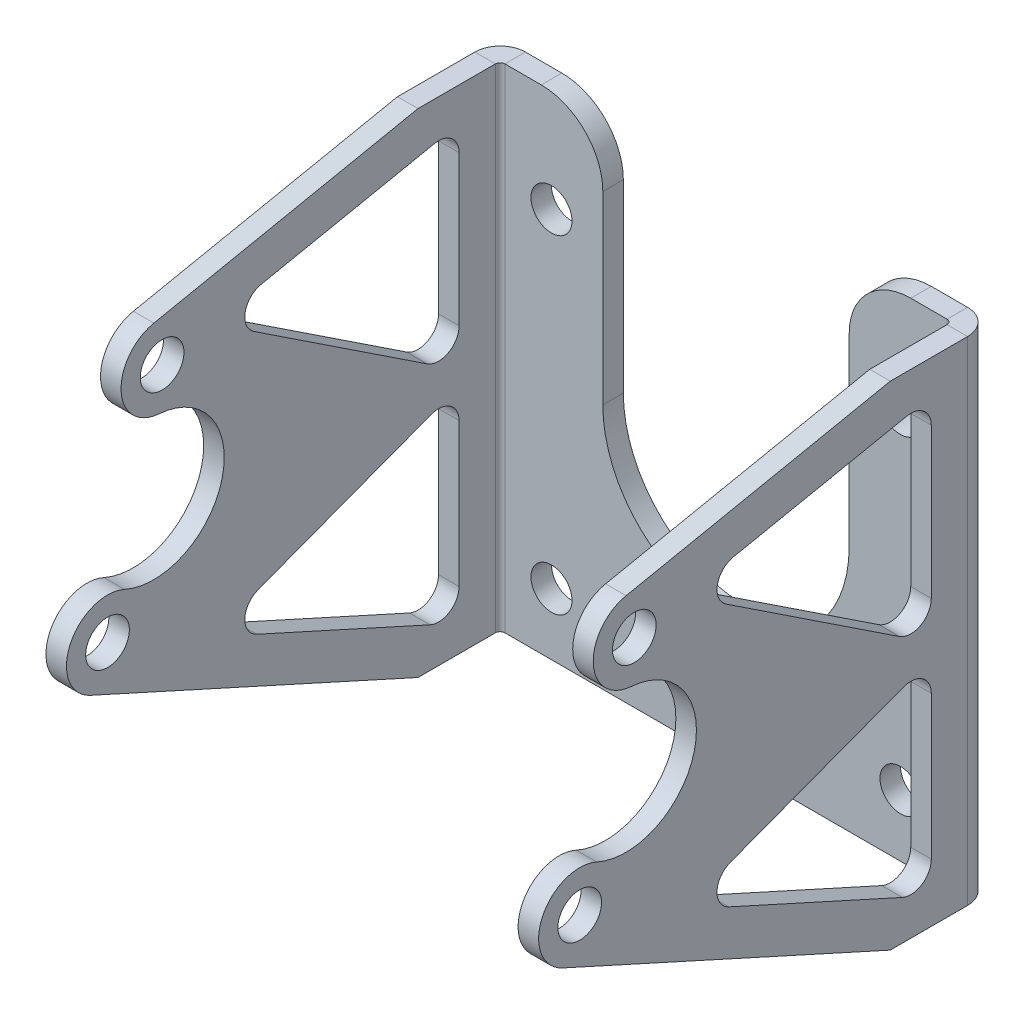
SolidWorks part; units mm, degrees
note: The reader was unsure of these and kept them because the rebuilt part matched: flange length of "Edge-Flange1".
ref_plane "Front Plane" through (0, 0, 0) normal (0, 0, 1) x (1, 0, 0)
ref_plane "Top Plane" through (0, 0, 0) normal (0, 1, 0) x (1, 0, 0)
ref_plane "Right Plane" through (0, 0, 0) normal (1, 0, 0) x (0, 0, -1)
sketch "Sketch4" plane through (0, 0, 0) normal (0, 0, 1) x (1, 0, 0)
  line L7 (38.4703, 37.2498) -> (28.9453, 37.2498)
  line L8 (19.4203, 27.7248) -> (19.4203, -0.8502)
  line L9 (-18.6797, -0.8502) -> (-18.6797, 27.7248)
  line L10 (-28.2047, 37.2498) -> (-37.7297, 37.2498)
  line L11 (-37.7297, 37.2498) -> (-37.7297, -38.9502)
  line L12 (-37.7297, -38.9502) -> (38.4703, -38.9502)
  line L13 (38.4703, -38.9502) -> (38.4703, 37.2498)
  arc A7 (28.9453, 37.2498) -> (19.4203, 27.7248) centre (28.9453, 27.7248) ccw
  arc A8 (-18.6797, -0.8502) -> (19.4203, -0.8502) centre (0.3703, -0.8502) ccw
  arc A9 (-18.6797, 27.7248) -> (-28.2047, 37.2498) centre (-28.2047, 27.7248) ccw
  circle A10 centre (-26.6172, -29.4252) radius 3.175
  circle A11 centre (27.3578, -29.4252) radius 3.175
  circle A12 centre (27.3578, 21.3748) radius 3.175
  circle A13 centre (-26.6172, 21.3748) radius 3.175
base flange "Base-Flange1" sketch "Sketch4" thickness 3.175 reverse thickness direction no parameters "D1"=0.7366
edge flange "Edge-Flange1" sketch "Sketch11" flange profiles "Sketch11", "Sketch20" flange angle 90 flange length 76.2 flange position material inside bend radius 0.7366 thickness 3.175 relief rectangular parameters "D6"=10, "D8"=0.254
sketch "Sketch11" plane through (38.4703, 0, 0) normal (-1, 0, 0) x (0, -1, 0)
  line L2 (-37.2498, 0) -> (-37.2498, 73.025)
  line L3 (-37.2498, 73.025) -> (38.9502, 73.025)
  line L4 (38.9502, 73.025) -> (38.9502, 0)
  line L5 (38.9502, 0) -> (-37.2498, 0) construction
  line L6 (38.9502, 0) -> (-37.2498, 0)
sketch "Sketch20" plane through (-37.7297, 0, 0) normal (1, 0, 0) x (0, 1, 0)
  line L0 (37.2498, 0) -> (-38.9502, 0) construction
  line L1 (37.2498, 0) -> (-38.9502, 0)
  line L2 (37.2498, 0) -> (37.2498, 73.025)
  line L3 (37.2498, 73.025) -> (-38.9502, 73.025)
  line L4 (-38.9502, 73.025) -> (-38.9502, 0)
bend "EdgeBend1" bend radius 0.7366 bend angle 90 parameters "D5"=1
bend "EdgeBend2" bend radius 0.7366 bend angle 90 parameters "D5"=3
sketch "Sketch18" plane through (38.4703, 0, 0) normal (1, 0, 0) x (0, 0, -1)
  line L7 (-12.7, 37.2498) -> (-53.5452, 28.9444)
  line L8 (-63.3386, -16.0187) -> (-12.7, -38.9502)
  line L13 (-12.7, -38.9502) -> (-73.025, -38.9502)
  line L14 (-73.025, 37.2498) -> (-0.7366, 37.2498) construction
  line L16 (-12.7, 37.2498) -> (-73.025, 37.2498)
  line L17 (-73.025, 37.2498) -> (-73.025, -38.9502)
  arc A3 (-53.5452, 28.9444) -> (-52.763, 16.3901) centre (-52.2799, 22.7217) ccw
  arc A4 (-58.0996, -4.4496) -> (-52.763, 16.3901) centre (-53.594, 5.4998) ccw
  arc A5 (-58.0996, -4.4496) -> (-63.3386, -16.0187) centre (-60.7191, -10.2341) ccw
  dimension "D5" = 6.35
  dimension "D7" = 10.922
  dimension "D8" = 6.35
  dimension "D3" = 40.8452
  dimension "D10" = 50.6386
extrude "Cut-Extrude2" cut sketch "Sketch18" against normal through all normal cut yes
sketch "Sketch21" plane through (38.4703, 0, 0) normal (1, 0, 0) x (0, 0, -1)
  line L8 (-10.644, -4.7382) -> (-37.4356, -14.8281)
  line L9 (-37.6263, -20.6916) -> (-10.8348, -32.8242)
  line L10 (-6.35, -29.9319) -> (-6.35, -7.7095)
  line L11 (-38.0693, 20.0803) -> (-11.2777, 2.3431)
  line L12 (-6.35, 4.9905) -> (-6.35, 28.1754)
  line L13 (-10.1577, 31.2868) -> (-36.9492, 25.839)
  line L14 (-53.5452, 28.9444) -> (-12.7, 37.2498) construction
  line L15 (3.175, 37.2498) -> (3.175, -38.9502) construction
  line L16 (-12.7, -38.9502) -> (-63.3386, -16.0187) construction
  arc A8 (-37.4356, -14.8281) -> (-37.6263, -20.6916) centre (-36.3166, -17.7994) ccw
  arc A9 (-10.8348, -32.8242) -> (-6.35, -29.9319) centre (-9.525, -29.9319) ccw
  arc A10 (-6.35, -7.7095) -> (-10.644, -4.7382) centre (-9.525, -7.7095) ccw
  arc A11 (-11.2777, 2.3431) -> (-6.35, 4.9905) centre (-9.525, 4.9905) ccw
  arc A12 (-6.35, 28.1754) -> (-10.1577, 31.2868) centre (-9.525, 28.1754) ccw
  arc A13 (-36.9492, 25.839) -> (-38.0693, 20.0803) centre (-36.3166, 22.7277) ccw
  circle A14 centre (-60.7191, -10.2341) radius 3.3782
  circle A15 centre (-52.2799, 22.7217) radius 3.3782
  dimension "D1" = 23.1849
  dimension "D3" = 32.1309
  dimension "D4" = 3.175
  dimension "D5" = 27.3398
  dimension "D2" = 3.175
  dimension "D6" = 3.175
  dimension "D8" = 3.175
  dimension "D10" = 3.175
  dimension "D11" = 3.175
  dimension "D17" = 6.7564
  dimension "D7" = 29.4107
  dimension "D9" = 28.6286
  dimension "D12" = 22.2224
  dimension "D13" = 6.35
  dimension "D14" = 9.525
  dimension "D15" = 6.35
  dimension "D16" = 9.525
extrude "Cut-Extrude3" cut sketch "Sketch21" against normal up to surface (76.2 mm away) normal cut yes up to face at (-37.7297, 2.5706, 31.6812)
sketch "Bend-Lines1" [suppressed] plane through (0, 0, 0) normal (0, 1, 0) x (1, 0, 0)
sketch "Bounding-Box1" [suppressed] plane through (0, 0, 0) normal (0, 1, 0) x (1, 0, 0)
sheet metal parameters "Sheet-Metal1" thickness 3.175 parameters "D1"=0.7366
flat pattern "Flat-Pattern1" [suppressed]
sketch "Bend-Lines2" plane through (0, 0, 0) normal (0, 1, 0) x (1, 0, 0)
sketch3d "Bounding-Box2" [suppressed]
  line L0 (66.675, -66.675, 0) -> (-9.525, -66.675, 0) construction
  line L1 (66.675, 9.525, 0) -> (-9.525, 9.525, 0) construction
  line L2 (66.675, -66.675, 0) -> (66.675, 9.525, 0) construction
  line L3 (-9.525, -66.675, 0) -> (-9.525, 9.525, 0) construction
sheet metal parameters "Sheet-Metal2" thickness 3.175 parameters "D1"=0.7366
flat pattern "Flat-Pattern1" [suppressed]
sketch "Bend-Lines2" plane through (0, 0, 0) normal (0, 0, 1) x (1, 0, 0)
  line L0 (36.384, -38.9502) -> (36.384, 37.2498) construction
  line L1 (36.384, -38.9502) -> (36.384, 37.2498) construction
sketch3d "Bounding-Box2" [suppressed]
  line L0 (-66.675, -66.675, 0) -> (81.5525, -66.675, 0) construction
  line L1 (-66.675, 9.525, 0) -> (81.5525, 9.525, 0) construction
  line L2 (-66.675, -66.675, 0) -> (-66.675, 9.525, 0) construction
  line L3 (81.5525, -66.675, 0) -> (81.5525, 9.525, 0) construction
bend of the flat pattern "Flatten-<EdgeBend1>1"
bend of the flat pattern "Flatten-<EdgeBend2>1"
sheet metal parameters "Sheet-Metal4" thickness 3.175 parameters "D1"=0.7366
flat pattern "Flat-Pattern1"
sketch "Bend-Lines2" plane through (0, 0, 0) normal (0, 0, 1) x (1, 0, 0)
  line L0 (36.384, -38.9502) -> (36.384, 37.2498) construction
  line L1 (36.384, -38.9502) -> (36.384, 37.2498) construction
  line L2 (-35.6434, 37.2498) -> (-35.6434, -38.9502) construction
  line L3 (-35.6434, 37.2498) -> (-35.6434, -38.9502) construction
sketch3d "Bounding-Box2" [suppressed]
  line L0 (-132.7465, -66.675, 0) -> (75.5965, -66.675, 0) construction
  line L1 (-132.7465, 9.525, 0) -> (75.5965, 9.525, 0) construction
  line L2 (-132.7465, -66.675, 0) -> (-132.7465, 9.525, 0) construction
  line L3 (75.5965, -66.675, 0) -> (75.5965, 9.525, 0) construction
bend of the flat pattern "Flatten-<EdgeBend1>1"
bend of the flat pattern "Flatten-<EdgeBend2>2"
sheet metal parameters "Sheet-Metal5" thickness 3.175 parameters "D1"=0.7366
flat pattern "Flat-Pattern1"
sketch "Bend-Lines2" plane through (0, 0, 0) normal (0, 0, 1) x (1, 0, 0)
  line L0 (36.384, -38.9502) -> (36.384, 37.2498) construction
  line L1 (36.384, -38.9502) -> (36.384, 37.2498) construction
  line L2 (-35.6434, 37.2498) -> (-35.6434, -38.9502) construction
  line L3 (-35.6434, 37.2498) -> (-35.6434, -38.9502) construction
sketch3d "Bounding-Box2" [suppressed]
  line L0 (-132.7465, -66.675, 0) -> (75.5965, -66.675, 0) construction
  line L1 (-132.7465, 9.525, 0) -> (75.5965, 9.525, 0) construction
  line L2 (-132.7465, -66.675, 0) -> (-132.7465, 9.525, 0) construction
  line L3 (75.5965, -66.675, 0) -> (75.5965, 9.525, 0) construction
bend of the flat pattern "Flatten-<EdgeBend1>1"
bend of the flat pattern "Flatten-<EdgeBend2>2"
